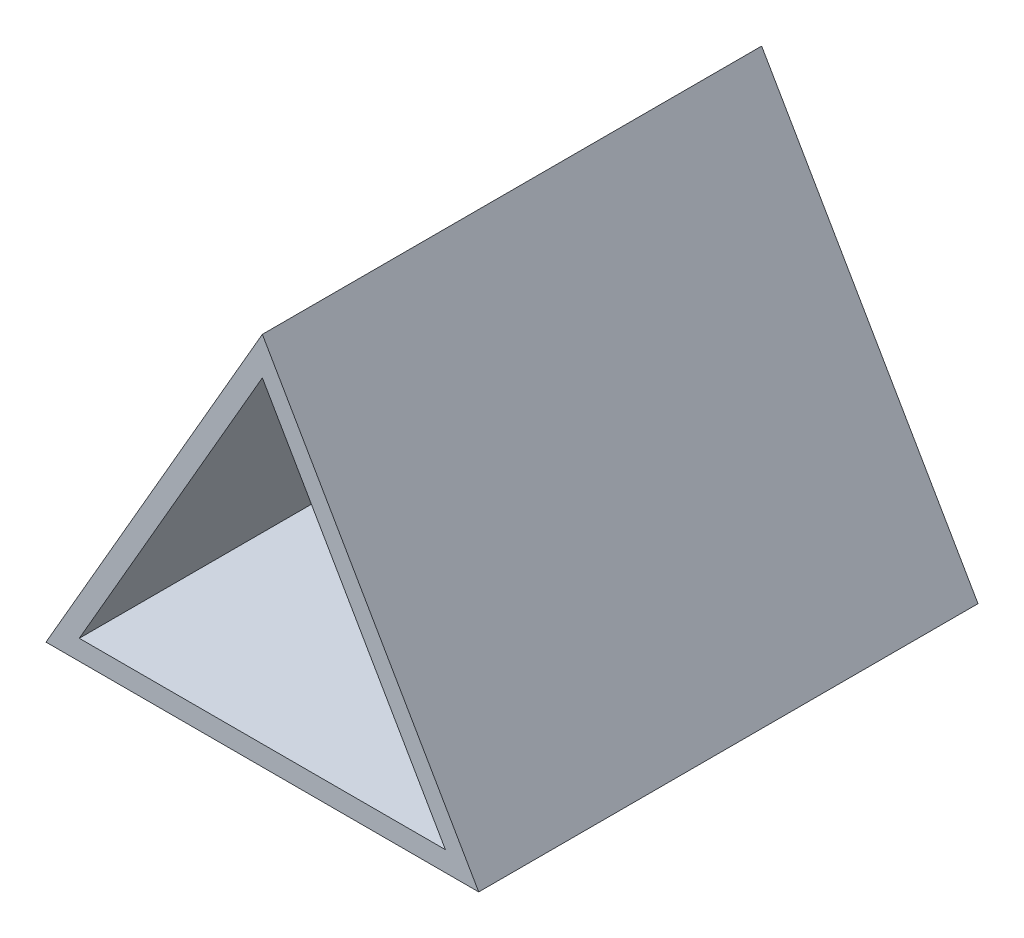
SolidWorks part; units mm, degrees
ref_plane "Front Plane" through (0, 0, 0) normal (0, 0, 1) x (1, 0, 0)
ref_plane "Top Plane" through (0, 0, 0) normal (0, 1, 0) x (1, 0, 0)
ref_plane "Right Plane" through (0, 0, 0) normal (1, 0, 0) x (0, 0, -1)
sketch "Sketch3" plane through (0, 0, 0) normal (0, 0, 1) x (1, 0, 0)
  line L0 (-122.5, 5.2209) -> (116.9494, 5.2209) construction
  line L1 (-122.5, 67.0491) -> (116.9494, 67.0491)
  line L2 (-122.5, 67.0491) -> (-122.5, -56.6072)
  line L3 (-122.5, -56.6072) -> (116.9494, -56.6072)
  line L4 (116.9494, 67.0491) -> (116.9494, -56.6072)
  line L5 (-2.7753, 67.0491) -> (-2.7753, -56.6072) construction
  line L6 (-25.2753, -7.7694) -> (-2.7753, 31.2017)
  line L12 (29.7247, -12.7791) -> (-35.2753, -12.7791)
  line L14 (-1.3522, 5.2209) -> (-2.7753, 6.644)
  line L18 (-2.7753, 31.2017) -> (19.7247, -7.7694)
  line L19 (19.7247, -7.7694) -> (-25.2753, -7.7694)
  line L20 (-25.2753, -7.7694) -> (8.4747, 11.7161) construction
  line L21 (19.7247, -7.7694) -> (-14.0253, 11.7161) construction
  line L22 (-2.7753, 31.2017) -> (-2.7753, 0) construction
  line L23 (-30.2753, -9.7791) -> (-2.7753, 37.8523)
  line L42 (24.7247, -9.7791) -> (-30.2753, -9.7791)
  line L43 (-2.7753, 37.8523) -> (24.7247, -9.7791)
  line L44 (-2.7753, 43.5126) -> (29.7247, -12.7791)
  line L45 (-35.2753, -12.7791) -> (-2.7753, 43.5126)
  point P4 (-65.9955, 5.2209)
  point P10 (-65.9955, 5.2209)
  point P13 (0, 40.6399)
  point P16 (-0.6651, 39.495)
  point P17 (35.8244, -19.084)
  point P20 (-2.7753, 5.2209)
  point P27 (7.7505, -5.3087)
  point P28 (-2.7753, 5.2209)
  point P31 (-35, -19.084)
  point P32 (-70, 0)
  point P37 (-32.9093, -19.084)
  point P38 (-70, 0)
  point P45 (34.468, -19.084)
  point P46 (-4.7886, 37.3527)
  point P47 (0, 0)
  point P49 (-40.8315, -18.6475)
  point P53 (-42.5, -18.6475)
  point P54 (-2.7753, 46.5528)
  point P55 (-2.7753, 44.4501)
  point P56 (40.8888, -18.6475)
  point P57 (40.0033, -17.3253)
  dimension "D2" = 55
  dimension "D3" = 65
  dimension "D1" = 15
  dimension "D4" = 18
  dimension "triangle3" = 45
  dimension "triangle2" = 45
  dimension "triangle" = 45
extrude "Boss-Extrude4" add sketch "Sketch3" against normal blind 75 rebuild error yes
extrude "Boss-Extrude5" add sketch "Sketch3<7>" against normal blind 75 contours L45 L12 L44 L23 L43 L42 region at (-2.7753, -11.9192, 0)
sketch "Sketch3<7>" plane through (0, 0, 0) normal (0, 0, 1) x (1, 0, 0) same geometry as "Sketch3"
